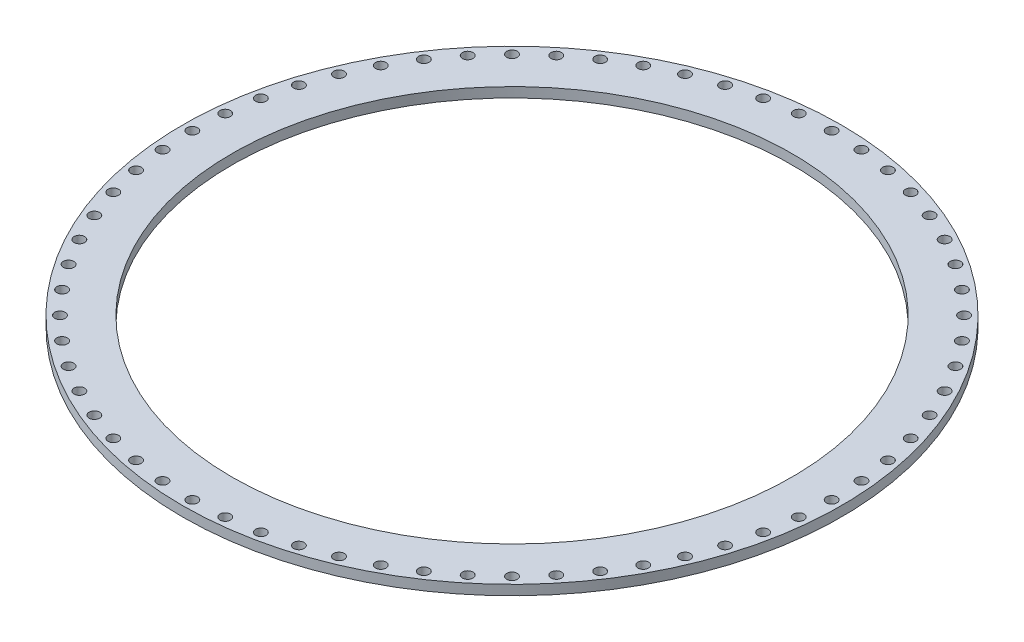
SolidWorks part; units mm, degrees
ref_plane "Front Plane" through (0, 0, 0) normal (0, 0, 1) x (1, 0, 0)
ref_plane "Top Plane" through (0, 0, 0) normal (0, 1, 0) x (1, 0, 0)
ref_plane "Right Plane" through (0, 0, 0) normal (1, 0, 0) x (0, 0, -1)
ref_axis "Axe1" through (0, 55, 0) along (0, -1, 0)
sketch "Esquisse2" plane through (0, 0, 0) normal (0, 0, 1) x (1, 0, 0)
  line L0 (0, 0) -> (100, 0)
  line L1 (100, 0) -> (100, 3)
  line L4 (100, 3) -> (0, 3)
  line L5 (0, 55) -> (0, -55) construction
  line L6 (0, 3) -> (0, 0)
  dimension "D1" = 100
  dimension "D3" = 3
revolve "MainRevolution" add sketch "Esquisse2" angle 360 about axis through (0, 55, 0) along (0, -1, 0)
sketch "Esquisse4" plane through (0, 3, 0) normal (0, 1, 0) x (1, 0, 0)
  circle A0 centre (0, 0) radius 85
  dimension "D1" = 170
extrude "CentralHole" cut sketch "Esquisse4" against normal through all
sketch "Esquisse5" plane through (0, 3, 0) normal (0, 1, 0) x (1, 0, 0)
  circle A0 centre (97, 0) radius 1.6
  dimension "D1" = 3.2
  dimension "D2" = 97
extrude "FixingHole" cut sketch "Esquisse5" against normal through all
pattern_circular "Répétition circulaire1" count 64 every 5.625 about axis through (0, 55, 0) along (0, -1, 0) of "FixingHole"
